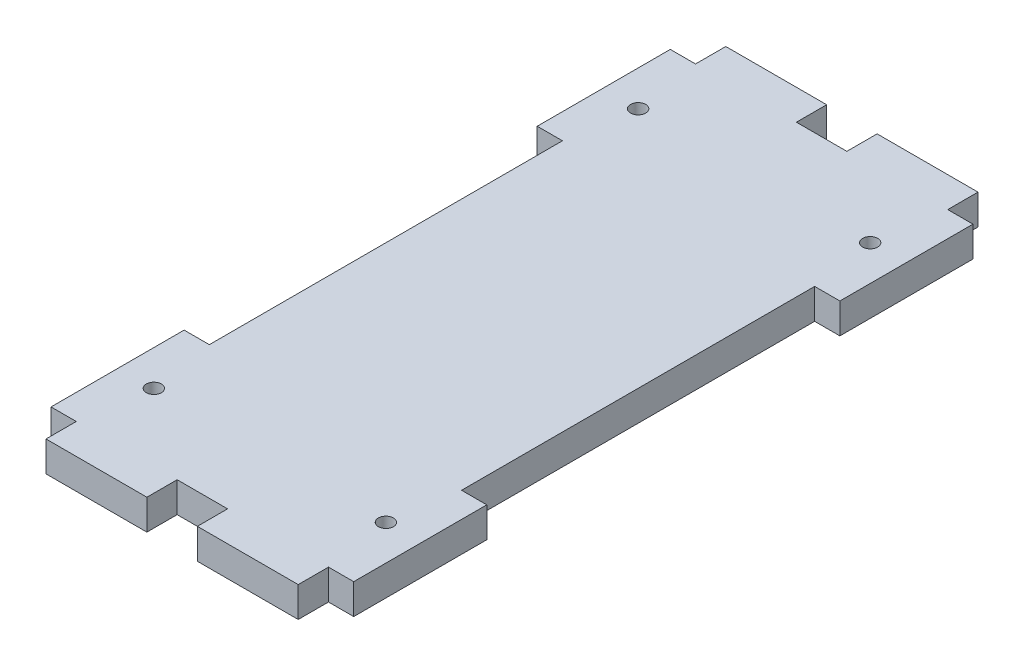
SolidWorks part; units mm, degrees
ref_plane "Plan de face" through (0, 0, 0) normal (0, 0, 1) x (1, 0, 0)
ref_plane "Plan de dessus" through (0, 0, 0) normal (0, 1, 0) x (1, 0, 0)
ref_plane "Plan de droite" through (0, 0, 0) normal (1, 0, 0) x (0, 0, -1)
sketch "Esquisse1" plane through (0, 0, 0) normal (0, 1, 0) x (1, 0, 0)
  line L0 (0, 89.2093) -> (0, -94.1785) construction
  line L1 (-30, 61.38) -> (30, 61.38)
  line L2 (-30, 61.38) -> (-30, -61.38)
  line L3 (-30, -61.38) -> (30, -61.38)
  line L4 (30, 61.38) -> (30, -61.38)
  dimension "D1" = 60
  dimension "D2" = 122.76
  dimension "D3" = 61.38
  dimension "D4" = 30
extrude "Boss.-Extru.1" add sketch "Esquisse1" along normal blind 6
sketch "Esquisse2" plane through (0, 6, 0) normal (0, 1, 0) x (1, 0, 0)
  line L0 (30, 61.38) -> (-30, 61.38) construction
  line L1 (-25, 61.38) -> (-5, 61.38)
  line L2 (-25, 61.38) -> (-25, 67.38)
  line L3 (-25, 67.38) -> (-5, 67.38)
  line L4 (-5, 61.38) -> (-5, 67.38)
  line L6 (5, 61.38) -> (25, 61.38)
  line L7 (5, 61.38) -> (5, 67.38)
  line L8 (5, 67.38) -> (25, 67.38)
  line L9 (25, 61.38) -> (25, 67.38)
  line L10 (-30, 61.38) -> (-30, -61.38) construction
  line L11 (30, -61.38) -> (30, 61.38) construction
  line L12 (-114.0924, 0) -> (165.6917, 0) construction
  line L13 (25, -61.38) -> (25, -67.38)
  line L14 (5, -67.38) -> (25, -67.38)
  line L15 (5, -61.38) -> (5, -67.38)
  line L16 (5, -61.38) -> (25, -61.38)
  line L17 (-5, -61.38) -> (-5, -67.38)
  line L18 (-25, -67.38) -> (-5, -67.38)
  line L19 (-25, -61.38) -> (-25, -67.38)
  line L20 (-25, -61.38) -> (-5, -61.38)
  dimension "D1" = 6
  dimension "D2" = 20
  dimension "D3" = 6
  dimension "D4" = 20
  dimension "D5" = 5
  dimension "D6" = 5
extrude "Boss.-Extru.2" add sketch "Esquisse2" against normal blind 6
sketch "Esquisse3" plane through (0, 6, 0) normal (0, 1, 0) x (1, 0, 0)
  line L0 (73.2715, 0) -> (-73.7315, 0) construction
  line L1 (-60.2107, 48) -> (82.7649, 48) construction
  line L2 (-25, 61.38) -> (-30, 61.38) construction
  line L3 (30, -61.38) -> (30, 61.38) construction
  circle A0 centre (23, 48) radius 1.5
  circle A1 centre (-23, 48) radius 1.5
  circle A2 centre (-23, -48) radius 1.5
  circle A3 centre (23, -48) radius 1.5
  point P5 (-27.5, 61.38)
  dimension "D3" = 3
  dimension "D4" = 3
  dimension "D5" = 46
  dimension "D1" = 13.38
  dimension "D2" = 7
extrude "Enlèv. mat.-Extru.1" cut sketch "Esquisse3" against normal blind 6
sketch "Esquisse4" plane through (0, 6, 0) normal (0, 1, 0) x (1, 0, 0)
  line L0 (-30, 61.38) -> (-30, -61.38) construction
  line L1 (-30, 35) -> (-25, 35)
  line L2 (-30, 35) -> (-30, -35)
  line L3 (-30, -35) -> (-25, -35)
  line L4 (-25, 35) -> (-25, -35)
  line L5 (0, 78.1772) -> (0, -74.3107) construction
  line L6 (-30, -61.38) -> (-25, -61.38) construction
  line L7 (25, 35) -> (25, -35)
  line L8 (30, -35) -> (25, -35)
  line L9 (30, 35) -> (30, -35)
  line L10 (30, 35) -> (25, 35)
  point P9 (-27.5, -61.38)
  dimension "D1" = 5
  dimension "D2" = 70
  dimension "D3" = 26.38
extrude "Enlèv. mat.-Extru.2" cut sketch "Esquisse4" against normal blind 6
equation "\"D3@Esquisse1\"=\"D2@Esquisse1\"/2"
equation "\"D4@Esquisse1\"=\"D1@Esquisse1\"/2"
